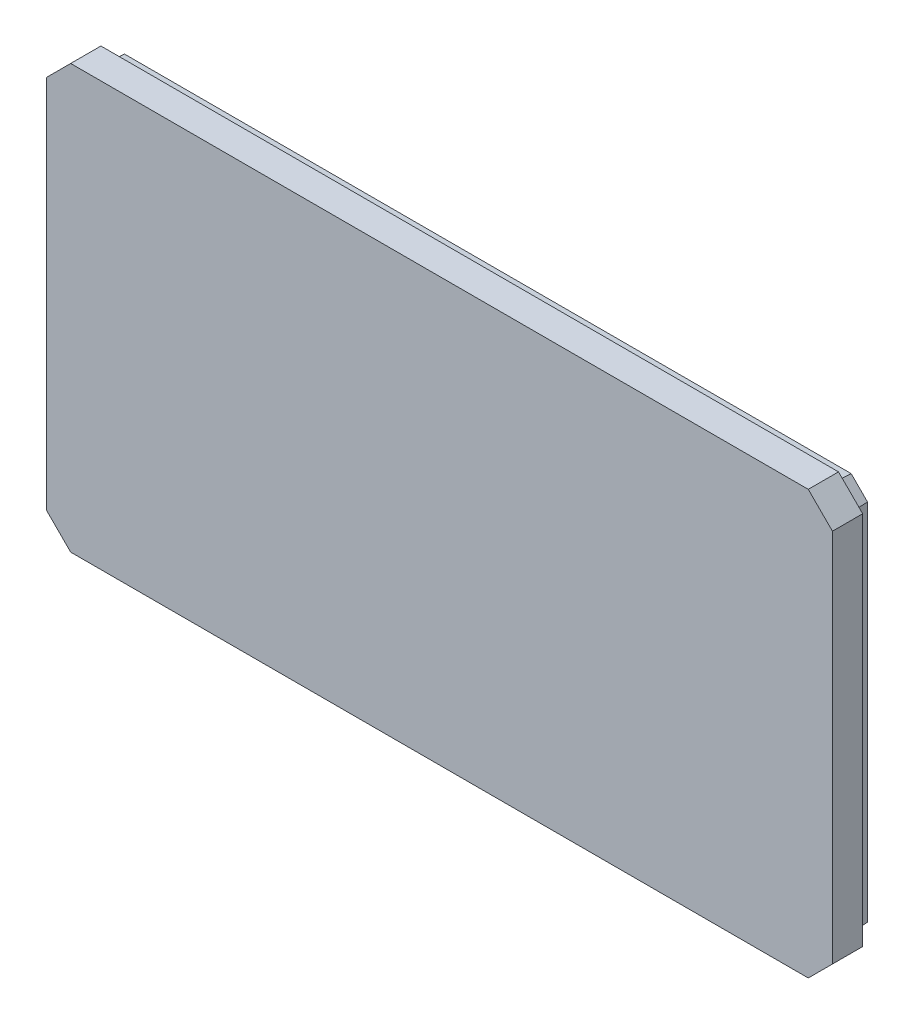
SolidWorks part; units mm, degrees
ref_plane "Alzado" through (0, 0, 0) normal (0, 0, 1) x (1, 0, 0)
ref_plane "Planta" through (0, 0, 0) normal (0, 1, 0) x (1, 0, 0)
ref_plane "Vista lateral" through (0, 0, 0) normal (1, 0, 0) x (0, 0, -1)
sketch "Croquis1" plane through (0, 0, 0) normal (0, 0, 1) x (1, 0, 0)
  line L1 (-32.5, -17.5) -> (32.5, -17.5)
  line L2 (-32.5, -17.5) -> (-32.5, 17.5)
  line L3 (-32.5, 17.5) -> (32.5, 17.5)
  line L4 (32.5, -17.5) -> (32.5, 17.5)
  line L5 (-32.5, -17.5) -> (32.5, 17.5) construction
  line L6 (-32.5, 17.5) -> (32.5, -17.5) construction
  point P0 (0, 0)
  dimension "D1" = 65
  dimension "D2" = 35
extrude "Saliente-Extruir1" add sketch "Croquis1" along normal blind 2.5 contours L2 L1 L4 L3
chamfer "Chamfer1" distance 2 angle 45 4 edges at (-32.5, -17.5, 1.25) (-32.5, 17.5, 1.25) (32.5, 17.5, 1.25) (32.5, -17.5, 1.25)
sketch "Sketch1" plane through (0, 0, 2.5) normal (0, 0, 1) x (1, 0, 0)
  line L0 (-29.6716, -15.5) -> (29.6716, -15.5)
  line L1 (29.6716, -15.5) -> (30.5, -14.6716)
  line L2 (30.5, -14.6716) -> (30.5, 14.6716)
  line L3 (30.5, 14.6716) -> (29.6716, 15.5)
  line L4 (29.6716, 15.5) -> (-29.6716, 15.5)
  line L5 (-29.6716, 15.5) -> (-30.5, 14.6716)
  line L6 (-30.5, 14.6716) -> (-30.5, -14.6716)
  line L7 (-30.5, -14.6716) -> (-29.6716, -15.5)
  line L8 (-32.5, 15.5) -> (-32.5, -15.5)
  line L9 (-32.5, -15.5) -> (-30.5, -17.5)
  line L10 (-30.5, -17.5) -> (30.5, -17.5)
  line L11 (30.5, -17.5) -> (32.5, -15.5)
  line L12 (32.5, -15.5) -> (32.5, 15.5)
  line L13 (32.5, 15.5) -> (30.5, 17.5)
  line L14 (30.5, 17.5) -> (-30.5, 17.5)
  line L15 (-30.5, 17.5) -> (-32.5, 15.5)
  line L16 (-32.5, 15.5) -> (-32.5, -15.5) construction
  line L17 (-32.5, -15.5) -> (-30.5, -17.5) construction
  line L18 (-30.5, -17.5) -> (30.5, -17.5) construction
  line L19 (30.5, -17.5) -> (32.5, -15.5) construction
  line L20 (32.5, -15.5) -> (32.5, 15.5) construction
  line L21 (32.5, 15.5) -> (30.5, 17.5) construction
  line L22 (30.5, 17.5) -> (-30.5, 17.5) construction
  line L23 (-30.5, 17.5) -> (-32.5, 15.5) construction
  line L24 (-30.0858, -16.5) -> (30.0858, -16.5)
  line L25 (30.0858, -16.5) -> (31.5, -15.0858)
  line L26 (31.5, -15.0858) -> (31.5, 15.0858)
  line L27 (31.5, 15.0858) -> (30.0858, 16.5)
  line L28 (30.0858, 16.5) -> (-30.0858, 16.5)
  line L29 (-30.0858, 16.5) -> (-31.5, 15.0858)
  line L30 (-31.5, 15.0858) -> (-31.5, -15.0858)
  line L31 (-31.5, -15.0858) -> (-30.0858, -16.5)
  dimension "D1" = 0
  dimension "D2" = 2
  dimension "D3" = 1
extrude "Boss-Extrude1" add sketch "Sketch1" against normal blind 1.5 from surface starting at face at (0, 0, 0)
chamfer "Chamfer2" distance 0.1 distance2 1.5 8 edges at (30.7929, 15.7929, -1.5) (0, 16.5, -1.5) (-30.7929, 15.7929, -1.5) (-31.5, 0, -1.5) (-30.7929, -15.7929, -1.5) (31.5, 0, -1.5) (30.7929, -15.7929, -1.5) (0, -16.5, -1.5) first distance on face at (0, 0, -1.5)
sketch "Sketch2" plane through (0, 0, 0) normal (0, 0, -1) x (-1, 0, 0)
  line L0 (-31.5, -15.0858) -> (-31.5, 15.0858) construction
  line L1 (-30.95, -1.05) -> (-32.05, -1.05)
  line L2 (-30.95, -1.05) -> (-30.95, 1.05)
  line L3 (-30.95, 1.05) -> (-32.05, 1.05)
  line L4 (-32.05, -1.05) -> (-32.05, 1.05)
  line L5 (-30.95, -1.05) -> (-32.05, 1.05) construction
  line L6 (-30.95, 1.05) -> (-32.05, -1.05) construction
  line L7 (31.5, 15.0858) -> (31.5, -15.0858) construction
  line L8 (32.05, -1.05) -> (30.95, -1.05)
  line L9 (32.05, -1.05) -> (32.05, 1.05)
  line L10 (32.05, 1.05) -> (30.95, 1.05)
  line L11 (30.95, -1.05) -> (30.95, 1.05)
  line L12 (32.05, -1.05) -> (30.95, 1.05) construction
  line L13 (32.05, 1.05) -> (30.95, -1.05) construction
  point P0 (-31.5, 0)
  point P7 (31.5, 0)
  dimension "D1" = 1.1
  dimension "D2" = 2.1
  dimension "D3" = 1.1
  dimension "D4" = 2.1
extrude "Cut-Extrude1" cut sketch "Sketch2" along normal blind 0.6
